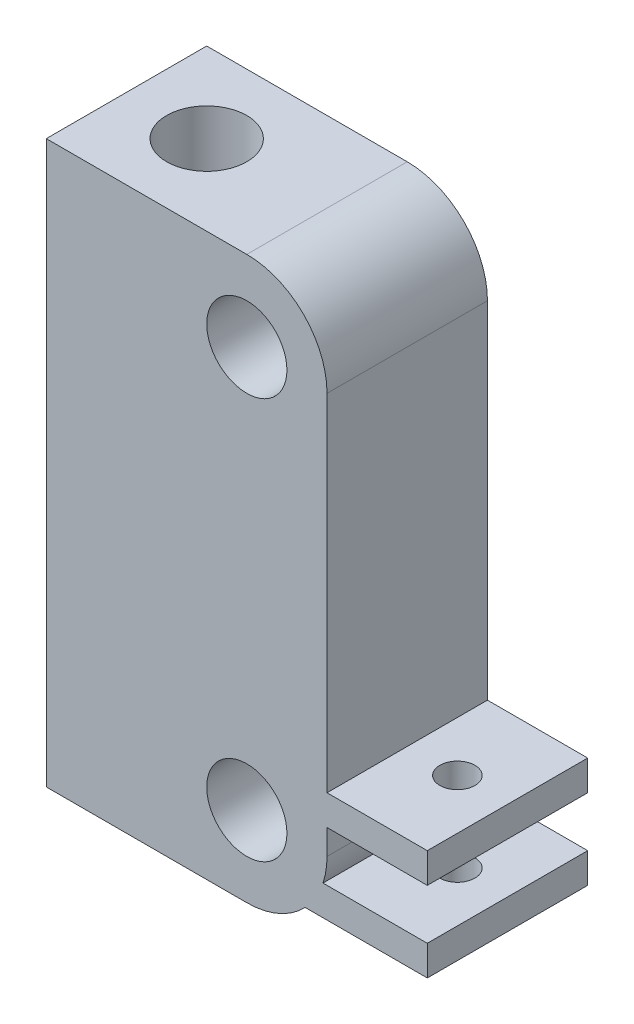
SolidWorks part; units mm, degrees
material "ABS"
ref_plane "Front Plane" through (0, 0, 0) normal (0, 0, 1) x (1, 0, 0)
ref_plane "Top Plane" through (0, 0, 0) normal (0, 1, 0) x (1, 0, 0)
ref_plane "Right Plane" through (0, 0, 0) normal (1, 0, 0) x (0, 0, -1)
sketch "Sketch1" plane through (0, 0, 0) normal (0, 0, 1) x (1, 0, 0)
  line L0 (11.942, -20.8688) -> (21.942, -20.8688)
  line L1 (-16.058, 21.6312) -> (3.942, 21.6312)
  line L2 (-16.058, 21.6312) -> (-16.058, -34.3688)
  line L3 (-16.058, -34.3688) -> (3.942, -34.3688)
  line L4 (11.942, 13.6312) -> (11.942, -20.8688)
  line L5 (21.942, -20.8688) -> (21.942, -23.8688)
  line L6 (21.942, -23.8688) -> (11.942, -23.8688)
  line L7 (9.7514, -31.8688) -> (21.942, -31.8688)
  line L8 (21.942, -31.8688) -> (21.942, -28.8688)
  line L9 (21.942, -28.8688) -> (11.5413, -28.8688)
  line L10 (11.942, -23.8688) -> (11.942, -26.3688)
  circle A0 centre (3.942, 13.6312) radius 4
  circle A1 centre (3.942, -26.3688) radius 4
  arc A2 (3.942, -34.3688) -> (9.7514, -31.8688) centre (3.942, -26.3688) ccw
  arc A3 (3.942, 21.6312) -> (11.942, 13.6312) centre (3.942, 13.6312) cw
  arc A4 (11.5413, -28.8688) -> (11.942, -26.3688) centre (3.942, -26.3688) ccw
  dimension "D1" = 8
  dimension "D2" = 8
  dimension "D8" = 8
  dimension "D3" = 40
  dimension "D4" = 8
  dimension "D5" = 8
  dimension "D6" = 8
  dimension "D7" = 8
  dimension "D9" = 28
  dimension "D10" = 3
  dimension "D11" = 3
  dimension "D12" = 2.5
  dimension "D13" = 5
  dimension "D14" = 10
extrude "Boss-Extrude1" add sketch "Sketch1" against normal blind 16
sketch "Sketch2" plane through (0, 21.6312, 0) normal (0, 1, 0) x (1, 0, 0)
  line L0 (3.942, 0) -> (-16.058, 0) construction
  line L1 (-16.058, 16) -> (-16.058, 0) construction
  circle A0 centre (-8.058, 8) radius 4
  dimension "D1" = 8
  dimension "D2" = 8
  dimension "D3" = 8
extrude "Cut-Extrude1" cut sketch "Sketch2" against normal through all
ref_point "Point1"
sketch "Sketch3" plane through (0, -20.8688, 0) normal (0, 1, 0) x (1, 0, 0)
  line L0 (21.942, 16) -> (21.942, 0) construction
  line L2 (21.942, 16) -> (11.942, 16) construction
  circle A0 centre (16.942, 8) radius 1.75
  dimension "D1" = 3.5
  dimension "D2" = 5
  dimension "D3" = 8
extrude "Cut-Extrude2" cut sketch "Sketch3" against normal through all
equation "\"rod_diameter\"= 8"
equation "\"rod_hole_thickness\"= 4"
equation "\"D1@Sketch1\"=\"rod_diameter\""
equation "\"D2@Sketch1\"=\"rod_diameter\""
equation "\"rod_radius\"= \"rod_diameter\" / 2"
equation "\"D4@Sketch1\"=\"rod_radius\"+\"rod_hole_thickness\""
equation "\"D5@Sketch1\"=\"rod_radius\"+\"rod_hole_thickness\""
equation "\"D6@Sketch1\"=\"rod_radius\"+\"rod_hole_thickness\""
equation "\"D7@Sketch1\"=\"rod_radius\"+\"rod_hole_thickness\""
equation "\"D8@Sketch1\"=\"rod_radius\"+\"rod_hole_thickness\""
equation "\"D9@Sketch1\"=\"rod_diameter\"*2 + \"rod_hole_thickness\"*3"
equation "\"D1@Boss-Extrude1\"= \"rod_diameter\" + \"rod_hole_thickness\" * 2"
equation "\"D1@Sketch2\"=\"rod_diameter\""
equation "\"D2@Sketch2\"=\"rod_radius\"+\"rod_hole_thickness\""
equation "\"D3@Sketch2\" = \"rod_radius\" + \"rod_hole_thickness\""
equation "\"platter_diameter\"= 320"
equation "\"platter_radius\"= \"platter_diameter\" / 2"
equation "\"extruder_mount_hole_spacing\"= 75"
equation "\"arm_rod_spacing\"= 40"
equation "\"D3@Sketch1\"=\"arm_rod_spacing\""
equation "\"D2@Sketch3\" = \"D14@Sketch1\" / 2"
equation "\"D3@Sketch3\"= \"D1@Boss-Extrude1\" / 2"
equation "\"top_frame_spacing\"= 100"
equation "\"motor_level_rod_spacing\"= 15"
equation "\"linear_bearing_diameter\"= 15"
equation "\"z_rod_spacing\"= 75"
equation "\"z_drive_rod_offset\"= 12"
equation "\"platter_rod_spacing\"= 50"
equation "\"rod_nut_thickness\"= 6.5"
equation "\"rod_nut_inscribed_diameter\"= 13"
equation "\"z_height\"= 400"
equation "\"gear_pitch\"=2"
equation "\"r_gear_teeth\"= 450"
equation "\"theta_gear_teeth\"= 385"
equation "\"sheet_thickness\"=5.333"
equation "\"sheet_tab_hole_thickness\"= \"sheet_thickness\""
equation "\"sheet_tab_width\"= \"sheet_thickness\"*2"
equation "\"sheet_double_tab_width\"= 35"
equation "\"sheet_bolt_diameter\"= 3"
equation "\"sheet_bolt_length\"= 16"
equation "\"sheet_nut_diameter\"= 5.5"
equation "\"sheet_nut_thickness\"= 2.5"
equation "\"sheet_nut_depth\"= 10"
equation "\"bearing_outside_diameter\"= 22"
equation "\"bearing_thickness\"= 7"
equation "\"corner_part_thickness\"= \"sheet_thickness\" + \"bearing_thickness\""
equation "\"setscrew_nut_diameter\"= 6"
equation "\"setscrew_nut_thickness\"= 3"
equation "\"setscrew_bolt_diameter\"= 3"
equation "\"motor_shaft_diameter\"= 5.7"
equation "\"printed_hole_tolerance\"= 0.5"
equation "\"D1@Sketch3\"=\"sheet_bolt_diameter\"+\"printed_hole_tolerance\""
